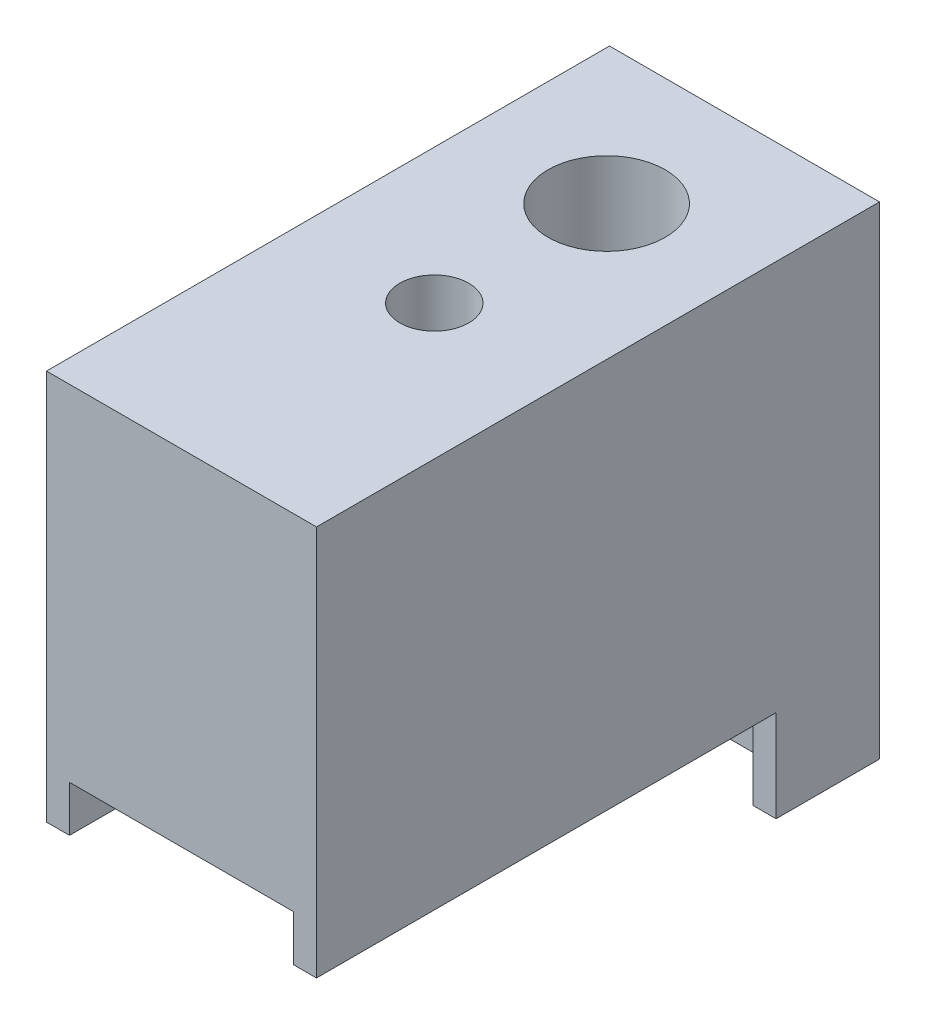
SolidWorks part; units mm, degrees
ref_plane "Front Plane" through (0, 0, 0) normal (0, 0, 1) x (1, 0, 0)
ref_plane "Top Plane" through (0, 0, 0) normal (0, 1, 0) x (1, 0, 0)
ref_plane "Right Plane" through (0, 0, 0) normal (1, 0, 0) x (0, 0, -1)
sketch "Sketch2" plane through (0, 0, 0) normal (1, 0, 0) x (0, 0, -1)
  line L0 (-44, 0) -> (0, 0)
  line L1 (0, 0) -> (0, -12)
  line L2 (-44, 0) -> (-44, 30)
  line L3 (-44, 30) -> (5, 30)
  line L4 (5, 30) -> (5, -12)
  line L5 (5, -12) -> (0, -12)
  dimension "D1" = 12
  dimension "D2" = 44
  dimension "D3" = 5
  dimension "D4" = 30
extrude "Boss-Extrude1" add sketch "Sketch2" along normal mid plane 19.5
sketch "Sketch3" plane through (9.75, 0, 0) normal (1, 0, 0) x (0, 0, -1)
  line L0 (-44, 30) -> (-44, -4)
  line L1 (-44, -4) -> (-4, -4)
  line L2 (-4, -4) -> (-4, -12)
  line L3 (-4, -12) -> (5, -12)
  line L6 (-44, 30) -> (5, 30)
  line L7 (5, 30) -> (5, -12)
  line L8 (0, 0) -> (0, -12) construction
  line L9 (-44, 0) -> (0, 0) construction
  dimension "D1" = 4
  dimension "D2" = 4
extrude "Boss-Extrude2" add sketch "Sketch3" along normal blind 2
mirror "Mirror1" about plane through (0, 0, 0) normal (1, 0, 0) of "Boss-Extrude2"
sketch "Sketch4" plane through (0, 0, 0) normal (0, -1, 0) x (1, 0, 0)
  line L0 (0, 0) -> (0, 7) construction
  line L1 (9.75, 0) -> (-9.75, 0) construction
  line L2 (0, 7) -> (0, 22) construction
  line L3 (0, 22) -> (0, 34) construction
  circle A0 centre (0, 34) radius 3.175 construction
  circle A1 centre (0, 22) radius 3
  circle A2 centre (0, 7) radius 5.1
  dimension "D1" = 6.35
  dimension "D5" = 6
  dimension "D6" = 10.2
  dimension "D2" = 7
  dimension "D3" = 15
  dimension "D4" = 12
extrude "Cut-Extrude1" cut sketch "Sketch4" against normal through all
